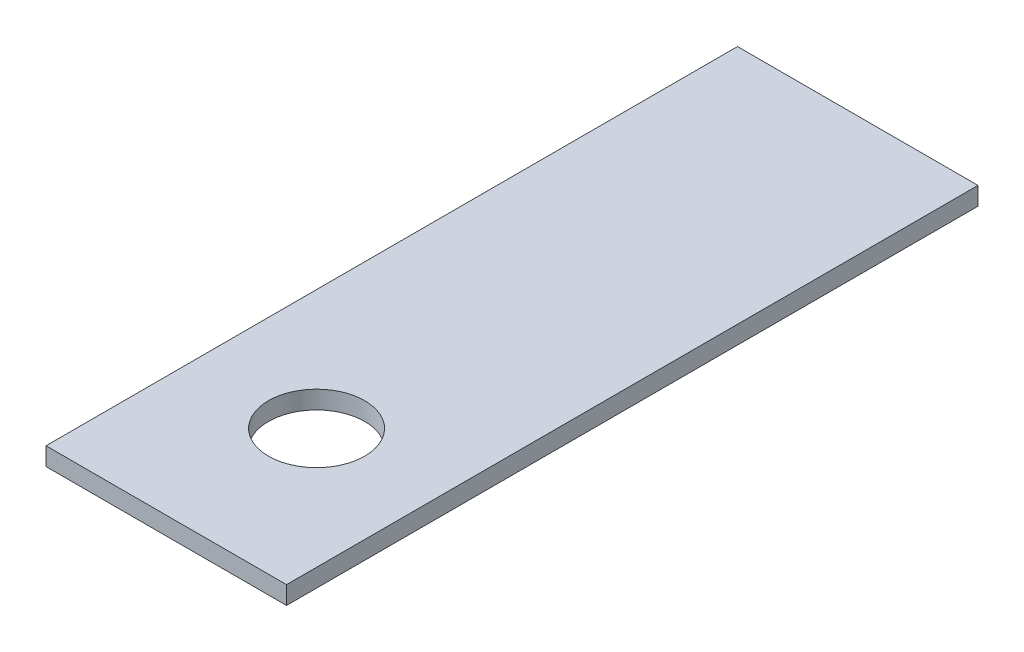
SolidWorks part; units mm, degrees
material "6061-T6 (SS)"
ref_plane "Front Plane" through (0, 0, 0) normal (0, 0, 1) x (1, 0, 0)
ref_plane "Top Plane" through (0, 0, 0) normal (0, 1, 0) x (1, 0, 0)
ref_plane "Right Plane" through (0, 0, 0) normal (1, 0, 0) x (0, 0, -1)
sketch "Sketch1" plane through (0, 0, 0) normal (0, 1, 0) x (1, 0, 0)
  line L1 (0, 0) -> (80, 0)
  line L2 (0, 0) -> (0, -230)
  line L3 (0, -230) -> (80, -230)
  line L4 (80, 0) -> (80, -230)
  dimension "D1" = 80
  dimension "D2" = 230
extrude "Boss-Extrude1" add sketch "Sketch1" along normal blind 6
sketch "Sketch5" plane through (0, 6, 0) normal (0, 1, 0) x (1, 0, 0)
  circle A0 centre (40, -180) radius 20 construction
  circle A1 centre (40, -180) radius 20
  point P1 (40, -180)
hole_wizard "Ø32.0 (32) Diameter Hole1" positions "Sketch5" profile "Sketch6" hole size "Ø32.0" standard "DIN" end condition through all
sketch "Sketch6" plane through (40, 6, 180) normal (1, 0, 0) x (0, 0, 1)
  line L0 (0, 0) -> (0, 6)
  line L1 (0, 6) -> (16, 6)
  line L2 (16, 6) -> (16, 0)
  line L5 (16, 0) -> (0, 0)
  line L11 (0, -6.35) -> (0, 107.95) construction
  dimension "Thru Hole Dia." = 32
  dimension "Thru Hole Depth" = 6
